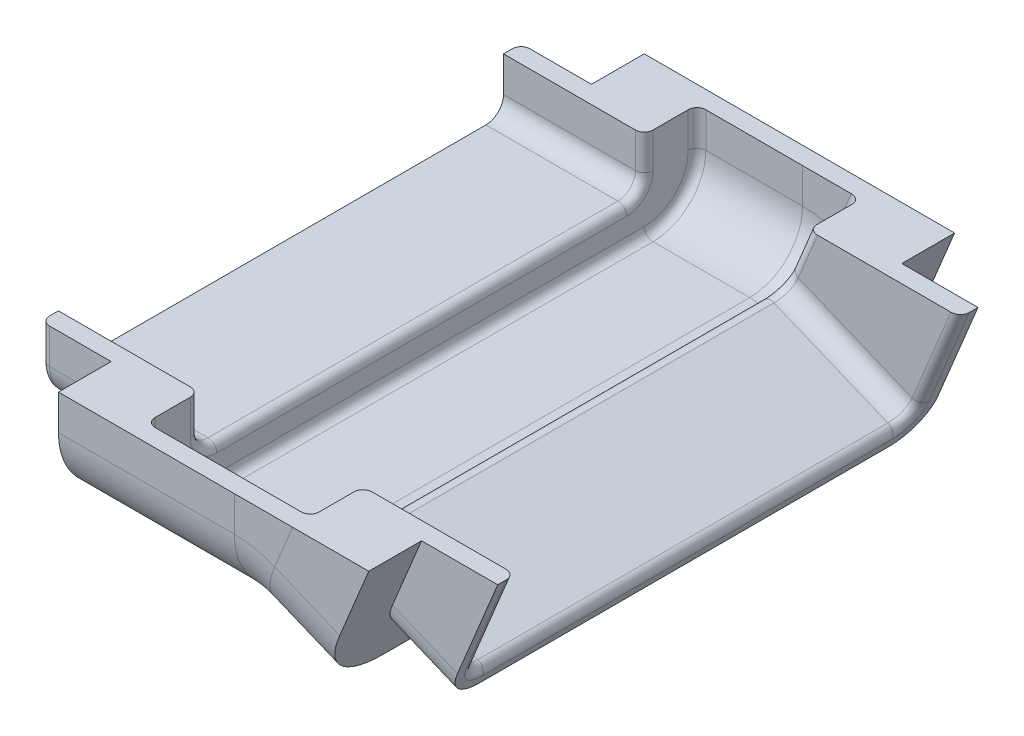
SolidWorks part; units mm, degrees
note: '?' marks a value the reader was unsure of.
ref_plane "Front" through (0, 0, 0) normal (0, 0, 1) x (1, 0, 0)
ref_plane "Top" through (0, 0, 0) normal (0, 1, 0) x (1, 0, 0)
ref_plane "Right" through (0, 0, 0) normal (1, 0, 0) x (0, 0, -1)
sketch "Sketch2path" plane through (0, 0, 0) normal (0, 0, 1) x (1, 0, 0)
  line L0 (13.8268, -0.7612) -> (17.5224, -2.2919)
  line L1 (0, 0) -> (10, 0)
  arc A1 (10, 0) -> (13.8268, -0.7612) centre (10, -10) cw
  point P5 (11.9891, 0)
  dimension "D1" = 10
  dimension "D2" = 22.5
  dimension "D4" = 10
  dimension "D3" = 4
sketch "Sketch3" plane through (0, 0, 0) normal (1, 0, 0) x (0, 0, -1)
  line L0 (-16.65, -4) -> (-16.65, 4)
  line L1 (-12.65, 8) -> (12.65, 8)
  line L2 (16.65, 4) -> (16.65, -4)
  line L3 (12.65, -8) -> (-12.65, -8)
  line L4 (-15.65, -4) -> (-15.65, 4)
  line L5 (12.65, -7) -> (-12.65, -7)
  line L6 (0, 91.8161) -> (0, -91.8161) construction
  line L12 (15.65, 4) -> (15.65, -4)
  line L13 (-12.65, 7) -> (12.65, 7)
  arc A0 (-12.65, 8) -> (-16.65, 4) centre (-12.65, 4) ccw
  arc A1 (16.65, 4) -> (12.65, 8) centre (12.65, 4) ccw
  arc A2 (12.65, -8) -> (16.65, -4) centre (12.65, -4) ccw
  arc A3 (-16.65, -4) -> (-12.65, -8) centre (-12.65, -4) ccw
  arc A4 (-12.65, 7) -> (-15.65, 4) centre (-12.65, 4) ccw
  arc A5 (12.65, 7) -> (15.65, 4) centre (12.65, 4) cw
  arc A6 (15.65, -4) -> (12.65, -7) centre (12.65, -4) cw
  arc A7 (-15.65, -4) -> (-12.65, -7) centre (-12.65, -4) ccw
  dimension "D1" = 4
sweep "Sweep1" add profiles "Sketch3" path "Sketch2path"
ref_point "Point1S1"
ref_point "Point2S3"
ref_axis "os podluzna S1" through (0, 0, 0) along (-1, 0, 0)?
ref_axis "os podluzna S3" through (17.5224, -2.2919, 0) along (0.9239, -0.3827, 0)?
ref_plane "Plane4 polowki" through (0, 0, 0) normal (0, 0, 1) x (1, 0, 0)
sketch "Sketch18" plane through (0, 0, 0) normal (-1, 0, 0) x (0, 0, 1)
  line L0 (0, -12.9502) -> (0, 11.9482)
  line L1 (0, -8.5584) -> (0, 8.5584) construction
  line L2 (8.92, -6) -> (-11.6506, -6) construction
  line L3 (9.3303, -5) -> (-11.6515, -5) construction
  line L4 (-15.65, -4) -> (-15.65, 4) construction
  line L6 (12.65, -7) -> (-12.65, -7) construction
  line L7 (-11.65, 5) -> (12.0326, 5) construction
  line L8 (-11.65, 6) -> (12.3851, 6) construction
  line L9 (-12.65, 7) -> (12.65, 7) construction
  line L10 (0, 0) -> (-18.9888, 0) construction
  line L11 (-13.65, -4.017) -> (-13.65, 4) construction
  line L12 (-12.65, -4.0133) -> (-12.65, 4) construction
  line L13 (-12.65, 0) -> (-13.65, 0)
  line L14 (0, 6) -> (0, 5)
  line L20 (-11.65, 6) -> (0, 6)
  line L23 (-13.65, 0) -> (-13.65, 4)
  line L24 (-11.65, 5) -> (0, 5)
  line L27 (-12.65, 0) -> (-12.65, 4)
  line L28 (12.65, 4.0061) -> (12.65, -3.9967) construction
  line L29 (13.65, 4.1386) -> (13.65, -4.0448) construction
  arc A23 (-11.65, 6) -> (-13.65, 4) centre (-11.65, 4) ccw
  arc A27 (-11.65, 5) -> (-12.65, 4) centre (-11.65, 4) ccw
  arc A28 (8.92, -6) -> (13.65, -4.0448) centre (10.7774, -3.7945) ccw construction
  arc A29 (9.3303, -5) -> (12.65, -3.9967) centre (10.7774, -3.7945) ccw construction
  arc A30 (13.65, 4.1386) -> (12.3851, 6) centre (10.5124, 3.3669) ccw construction
  arc A31 (12.65, 4.0061) -> (12.0326, 5) centre (10.5124, 3.3669) ccw construction
  arc A32 (-13.65, -4.017) -> (-11.6506, -6) centre (-11.6542, -4.0042) ccw construction
  arc A33 (-12.65, -4.0133) -> (-11.6515, -5) centre (-11.6542, -4.0042) ccw construction
  dimension "D1" = 2
  dimension "D3" = 1
  dimension "D4" = 1
extrude "Boss-Extrude6" add sketch "Sketch18" along normal mid plane 8 separate body contours A27 L24 L0 L20 A23 L23 L13 L27
mirror "Mirror6" about plane through (0, 0, 0) normal (0, 0, 1) of bodies 189
mirror "Mirror7" about plane through (-4, 0, 0) normal (0, -1, 0) of bodies 190 189
sketch "Sketch19" plane through (0, 0, 0) normal (-1, 0, 0) x (0, 0, 1)
  line L0 (-15.65, -4) -> (-15.65, 4) construction
  line L1 (12.65, -7) -> (-12.65, -7) construction
  line L2 (15.65, 4) -> (15.65, -4) construction
  line L3 (-12.65, 7) -> (12.65, 7) construction
  line L4 (-15.65, -4) -> (-15.65, 4)
  line L5 (12.65, -7) -> (-12.65, -7)
  line L6 (15.65, 4) -> (15.65, -4)
  line L7 (-12.65, 7) -> (12.65, 7)
  line L8 (-13.65, -4) -> (-13.65, 4) construction
  line L9 (-11.65, -6) -> (11.65, -6) construction
  line L10 (13.65, -4) -> (13.65, 4) construction
  line L11 (-11.65, 6) -> (11.65, 6) construction
  line L12 (-13.65, -4) -> (-13.65, 4)
  line L13 (-11.65, -6) -> (11.65, -6)
  line L14 (13.65, -4) -> (13.65, 4)
  line L15 (-11.65, 6) -> (11.65, 6)
  arc A0 (-15.65, -4) -> (-12.65, -7) centre (-12.65, -4) ccw construction
  arc A1 (12.65, -7) -> (15.65, -4) centre (12.65, -4) ccw construction
  arc A2 (15.65, 4) -> (12.65, 7) centre (12.65, 4) ccw construction
  arc A3 (-12.65, 7) -> (-15.65, 4) centre (-12.65, 4) ccw construction
  arc A4 (-15.65, -4) -> (-12.65, -7) centre (-12.65, -4) ccw
  arc A5 (12.65, -7) -> (15.65, -4) centre (12.65, -4) ccw
  arc A6 (15.65, 4) -> (12.65, 7) centre (12.65, 4) ccw
  arc A7 (-12.65, 7) -> (-15.65, 4) centre (-12.65, 4) ccw
  arc A8 (-13.65, -4) -> (-11.65, -6) centre (-11.65, -4) ccw construction
  arc A9 (11.65, -6) -> (13.65, -4) centre (11.65, -4) ccw construction
  arc A10 (13.65, 4) -> (11.65, 6) centre (11.65, 4) ccw construction
  arc A11 (-11.65, 6) -> (-13.65, 4) centre (-11.65, 4) ccw construction
  arc A12 (-13.65, -4) -> (-11.65, -6) centre (-11.65, -4) ccw
  arc A13 (11.65, -6) -> (13.65, -4) centre (11.65, -4) ccw
  arc A14 (13.65, 4) -> (11.65, 6) centre (11.65, 4) ccw
  arc A15 (-11.65, 6) -> (-13.65, 4) centre (-11.65, 4) ccw
extrude "Boss-Extrude7" add sketch "Sketch19" against normal blind 4
fillet "Fillet5" radius 0.5 24 edges at (4, -6.1213, -14.7713) (4, 0, -15.65) (4, 6.1213, -14.7713) (4, 7, 0) (4, 6.1213, 14.7713) (4, 0, 15.65) (4, -6.1213, 14.7713) (4, -7, 0) (-4, 0, -13.65) (-4, 6, 0) (-4, 5.4142, 13.0642) (-4, -5.4142, -13.0642) (4, 5, 0) (4, 0, -12.65) (-4, -6, 0) (-4, -5.4142, 13.0642) (-4, 0, 13.65) (-4, 5.4142, -13.0642) (4, 4.7071, -12.3571) (4, -5, 0) (4, -4.7071, 12.3571) (4, 0, 12.65) (4, 4.7071, 12.3571) (4, -4.7071, -12.3571)
ref_plane "Plane1" through (1.7558, 4.2388, 0) normal (0.3827, 0.9239, 0) x (0.9239, -0.3827, 0)
sketch "Sketch20" plane through (15.7666, -6.5307, 0) normal (0.9239, -0.3827, 0) x (0, 0, -1)
  line L0 (-12.65, 8.588) -> (-12.65, 4.588)
  line L1 (-13.65, 8.588) -> (-13.65, 4.588)
  line L2 (-12.65, 4.588) -> (-13.65, 4.588)
  line L3 (0, 9.588) -> (0, 10.588)
  line L5 (12.65, 9.588) -> (-12.65, 9.588) construction
  line L7 (0, 10.588) -> (-11.65, 10.588)
  line L8 (-13.65, 8.588) -> (-13.65, 0.588)
  line L9 (-12.65, -0.412) -> (12.65, -0.412)
  line L10 (13.65, 0.588) -> (13.65, 8.588)
  line L11 (12.65, 9.588) -> (-12.65, 9.588)
  line L12 (-13.65, 8.588) -> (-13.65, 4.588)
  line L13 (12.65, 10.588) -> (-12.65, 10.588) construction
  line L15 (0, 9.588) -> (-11.65, 9.588)
  line L16 (0, 4.588) -> (-19.8405, 4.588) construction
  line L17 (0, 4.588) -> (0, 5.0044)
  line L18 (0, 8.5584) -> (0, -8.5584) construction
  line L19 (0, 4.588) -> (0, 15.4955) construction
  line L20 (-14.65, 8.588) -> (-14.65, 0.588) construction
  line L21 (-13.65, 8.588) -> (-13.65, 0.588) construction
  line L22 (-12.65, -1.412) -> (12.65, -1.412) construction
  line L23 (-12.65, -0.412) -> (12.65, -0.412) construction
  line L24 (13.65, 0.588) -> (13.65, 8.588) construction
  line L25 (14.65, 0.588) -> (14.65, 8.588) construction
  arc A0 (-11.65, 10.588) -> (-13.65, 8.588) centre (-11.65, 8.588) ccw
  arc A1 (-11.65, 9.588) -> (-12.65, 8.588) centre (-11.65, 8.588) ccw
  arc A8 (-12.65, 9.588) -> (-13.65, 8.588) centre (-12.65, 8.588) ccw
  arc A9 (-13.65, 0.588) -> (-12.65, -0.412) centre (-12.65, 0.588) ccw
  arc A10 (12.65, -0.412) -> (13.65, 0.588) centre (12.65, 0.588) ccw
  arc A11 (13.65, 8.588) -> (12.65, 9.588) centre (12.65, 8.588) ccw
  arc A16 (-13.65, 0.588) -> (-12.65, -0.412) centre (-12.65, 0.588) ccw construction
  arc A17 (-14.65, 0.588) -> (-12.65, -1.412) centre (-12.65, 0.588) ccw construction
  arc A18 (12.65, -0.412) -> (13.65, 0.588) centre (12.65, 0.588) ccw construction
  arc A19 (12.65, -1.412) -> (14.65, 0.588) centre (12.65, 0.588) ccw construction
  arc A20 (14.65, 8.588) -> (12.65, 10.588) centre (12.65, 8.588) ccw construction
  arc A21 (13.65, 8.588) -> (12.65, 9.588) centre (12.65, 8.588) ccw construction
  arc A22 (-12.65, 10.588) -> (-14.65, 8.588) centre (-12.65, 8.588) ccw construction
  arc A23 (-12.65, 9.588) -> (-13.65, 8.588) centre (-12.65, 8.588) ccw construction
  dimension "D1" = 2
  dimension "D2" = 1
extrude "Boss-Extrude8" add sketch "Sketch20" along normal mid plane 8 separate body contours A1 L15 L3 L7 A0 L1 L2 L0
mirror "Mirror8" about plane through (1.7558, 4.2388, 0) normal (0.3827, 0.9239, 0) of bodies 194
mirror "Mirror9" about plane through (0, 0, 0) normal (0, 0, 1) of bodies 195
sketch "Sketch21" plane through (15.7666, -6.5307, 0) normal (0.9239, -0.3827, 0) x (0, 0, -1)
  line L0 (-15.65, 8.588) -> (-15.65, 0.588) construction
  line L1 (12.65, 11.588) -> (-12.65, 11.588) construction
  line L2 (15.65, 0.588) -> (15.65, 8.588) construction
  line L3 (-12.65, -2.412) -> (12.65, -2.412) construction
  line L4 (-15.65, 8.588) -> (-15.65, 0.588)
  line L5 (12.65, 11.588) -> (-12.65, 11.588)
  line L6 (15.65, 0.588) -> (15.65, 8.588)
  line L7 (-12.65, -2.412) -> (12.65, -2.412)
  line L8 (-13.65, 8.588) -> (-13.65, 0.588) construction
  line L9 (11.65, 10.588) -> (-11.65, 10.588) construction
  line L10 (13.65, 8.588) -> (13.65, 0.588) construction
  line L11 (11.65, -1.412) -> (-11.65, -1.412) construction
  line L12 (-13.65, 8.588) -> (-13.65, 0.588)
  line L13 (11.65, 10.588) -> (-11.65, 10.588)
  line L14 (13.65, 8.588) -> (13.65, 0.588)
  line L15 (11.65, -1.412) -> (-11.65, -1.412)
  arc A0 (-12.65, 11.588) -> (-15.65, 8.588) centre (-12.65, 8.588) ccw construction
  arc A1 (15.65, 8.588) -> (12.65, 11.588) centre (12.65, 8.588) ccw construction
  arc A2 (12.65, -2.412) -> (15.65, 0.588) centre (12.65, 0.588) ccw construction
  arc A3 (-15.65, 0.588) -> (-12.65, -2.412) centre (-12.65, 0.588) ccw construction
  arc A4 (-12.65, 11.588) -> (-15.65, 8.588) centre (-12.65, 8.588) ccw
  arc A5 (15.65, 8.588) -> (12.65, 11.588) centre (12.65, 8.588) ccw
  arc A6 (12.65, -2.412) -> (15.65, 0.588) centre (12.65, 0.588) ccw
  arc A7 (-15.65, 0.588) -> (-12.65, -2.412) centre (-12.65, 0.588) ccw
  arc A8 (-11.65, 10.588) -> (-13.65, 8.588) centre (-11.65, 8.588) ccw construction
  arc A9 (13.65, 8.588) -> (11.65, 10.588) centre (11.65, 8.588) ccw construction
  arc A10 (11.65, -1.412) -> (13.65, 0.588) centre (11.65, 0.588) ccw construction
  arc A11 (-13.65, 0.588) -> (-11.65, -1.412) centre (-11.65, 0.588) ccw construction
  arc A12 (-11.65, 10.588) -> (-13.65, 8.588) centre (-11.65, 8.588) ccw
  arc A13 (13.65, 8.588) -> (11.65, 10.588) centre (11.65, 8.588) ccw
  arc A14 (11.65, -1.412) -> (13.65, 0.588) centre (11.65, 0.588) ccw
  arc A15 (-13.65, 0.588) -> (-11.65, -1.412) centre (-11.65, 0.588) ccw
extrude "Boss-Extrude9" add sketch "Sketch21" against normal blind 4
fillet "Fillet6" radius 0.5 24 edges at (23.0192, 0.5261, 12.3571) (23.1313, 0.7967, 0) (21.2179, -3.8227, 12.65) (23.0192, 0.5261, -12.3571) (21.2179, -3.8227, -12.65) (19.3045, -8.4421, 0) (19.4165, -8.1715, 12.3571) (15.6282, 3.5876, 12.3571) (13.8268, -0.7612, 12.65) (12.0255, -5.11, -12.3571) (15.7403, 3.8582, 0) (12.0255, -5.11, 12.3571) (11.9134, -5.3806, 0) (15.6282, 3.5876, -12.3571) (13.8268, -0.7612, -12.65) (19.4165, -8.1715, -12.3571) (16.1694, 4.8942, 14.7713) (13.8268, -0.7612, 15.65) (11.4843, -6.4166, 14.7713) (11.1481, -7.2284, 0) (11.4843, -6.4166, -14.7713) (13.8268, -0.7612, -15.65) (16.1694, 4.8942, -14.7713) (16.5056, 5.706, 0)
ref_plane "Plane2" through (0, -2, 0) normal (0, 1, 0) x (1, 0, 0)
other "SurfaceCut1" flip cut yes
